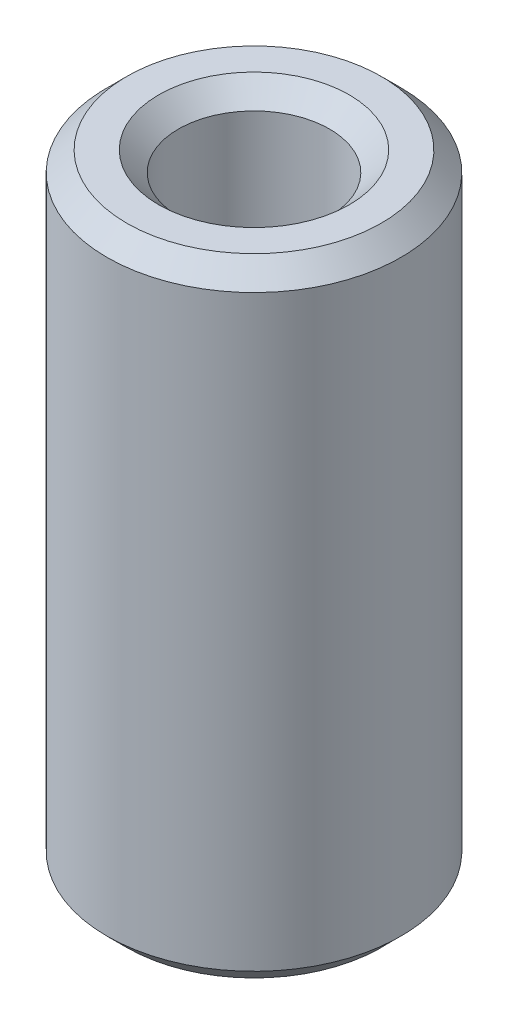
SolidWorks part; units mm, degrees
ref_plane "Front Plane" through (0, 0, 0) normal (0, 0, 1) x (1, 0, 0)
ref_plane "Top Plane" through (0, 0, 0) normal (0, 1, 0) x (1, 0, 0)
ref_plane "Right Plane" through (0, 0, 0) normal (1, 0, 0) x (0, 0, -1)
sketch "Sketch1" plane through (0, 0, 0) normal (0, 1, 0) x (1, 0, 0)
  circle A0 centre (0, 0) radius 10
  dimension "SLEEVE_OD" = 20
extrude "Boss-Extrude1" add sketch "Sketch1" along normal blind 42.6871
sketch "Sketch2" plane through (0, 0, 0) normal (0, 1, 0) x (1, 0, 0)
  circle A0 centre (0, 0) radius 5.1414
  dimension "BORE_D" = 10.2827
extrude "Cut-Extrude1" cut sketch "Sketch2" along normal through all
chamfer "Chamfer1" distance 1.3427 angle 45 4 edges at (0, 42.6871, 5.1414) (0, 0, 5.1414) (0, 0, 10) (0, 42.6871, 10)
